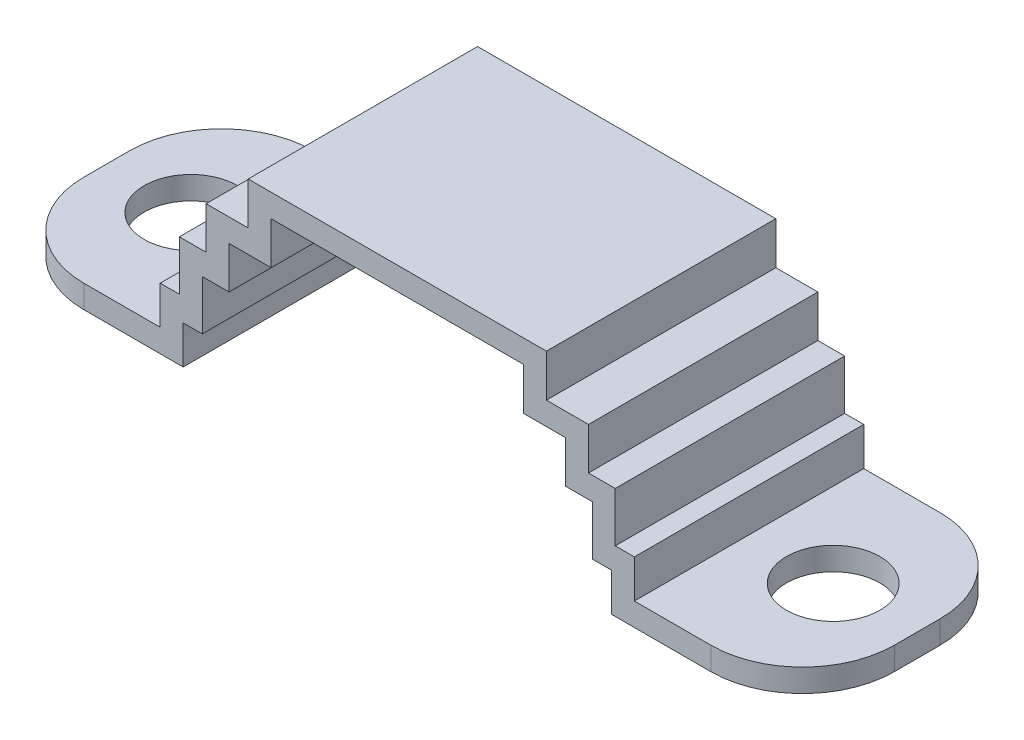
SolidWorks part; units mm, degrees
ref_plane "Front Plane" through (0, 0, 0) normal (0, 0, 1) x (1, 0, 0)
ref_plane "Top Plane" through (0, 0, 0) normal (0, 1, 0) x (1, 0, 0)
ref_plane "Right Plane" through (0, 0, 0) normal (1, 0, 0) x (0, 0, -1)
sketch "Sketch1" plane through (0, 0, 0) normal (0, 0, 1) x (1, 0, 0)
  line L0 (-53, 4.5) -> (-28, 4.5)
  line L1 (-28, 4.5) -> (-28, 9.5)
  line L2 (-28, 9.5) -> (-25.5, 9.5)
  line L3 (-25.5, 9.5) -> (-25.5, 16)
  line L4 (-25.5, 16) -> (-22, 16)
  line L5 (-22, 16) -> (-22, 21.5)
  line L6 (-22, 21.5) -> (-16.5, 21.5)
  line L7 (-16.5, 21.5) -> (-16.5, 27.05)
  line L8 (-16.5, 27.05) -> (0, 27.05)
  circle A0 centre (0, 0) radius 27.05
  dimension "D1" = 54.1
  dimension "D2" = 25
  dimension "D3" = 4.5
  dimension "D4" = 28
  dimension "D5" = 5
  dimension "D6" = 2.5
  dimension "D7" = 6.5
  dimension "D8" = 3.5
  dimension "D9" = 5.5
  dimension "D10" = 5.5
  dimension "D11" = 16.5
  dimension "D12" = 5.55
extrude "Extrude-Thin1" add sketch "Sketch1" along normal mid plane 30 thin contours L0 L1 L2 L3 L4 L5 L6 L7 L8 thin type one direction reverse wall 3
sketch "Sketch2" plane through (0, 7.5, 0) normal (0, 1, 0) x (1, 0, 0)
  line L0 (0, -15) -> (0, 15) construction
  circle A0 centre (-42, 0) radius 6.1
  dimension "D1" = 12.2
  dimension "D2" = 42
extrude "Cut-Extrude1" cut sketch "Sketch2" against normal through all
fillet "Fillet1" radius 12 2 edges at (-53, 6, -15) (-53, 6, 15)
mirror "Mirror1" about plane through (0, 30.05, 15) normal (1, 0, 0) of "Fillet1", "Cut-Extrude1", "Extrude-Thin1"
